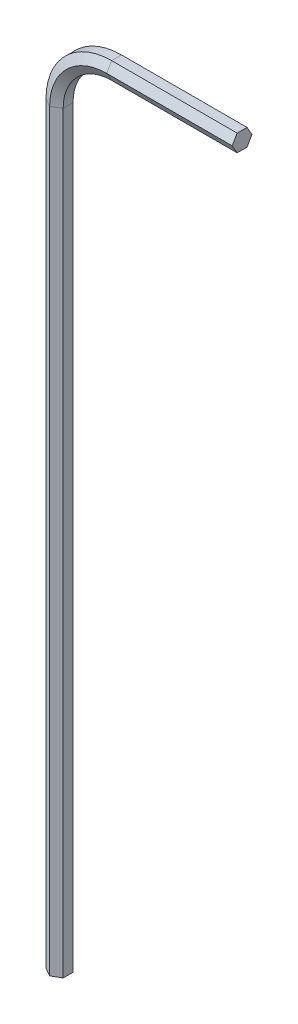
SolidWorks part; units mm, degrees
material "6061-T6 (SS)"
ref_plane "Front Plane" through (0, 0, 0) normal (0, 0, 1) x (1, 0, 0)
ref_plane "Top Plane" through (0, 0, 0) normal (0, 1, 0) x (1, 0, 0)
ref_plane "Right Plane" through (0, 0, 0) normal (1, 0, 0) x (0, 0, -1)
ref_axis "Axis1" through (0, 0, 55) along (0, 0, -1)
sketch "Sketch1" plane through (0, 0, 0) normal (0, 1, 0) x (1, 0, 0)
  line L1 (0.75, -0.433) -> (0.75, 0.433)
  line L2 (0.75, 0.433) -> (0, 0.866)
  line L3 (0, 0.866) -> (-0.75, 0.433)
  line L4 (-0.75, 0.433) -> (-0.75, -0.433)
  line L5 (-0.75, -0.433) -> (0, -0.866)
  line L6 (0, -0.866) -> (0.75, -0.433)
  circle A0 centre (0, 0) radius 0.75 construction
  dimension "D1" = 1.5
sketch "Sketch2" plane through (0, 0, 0) normal (0, 0, 1) x (1, 0, 0)
  line L0 (0, 0) -> (0, 66)
  line L1 (5, 71) -> (16, 71)
  arc A0 (0, 66) -> (5, 71) centre (5, 66) cw
  point P6 (0, 71)
  dimension "D3" = 5
  dimension "D1" = 71
  dimension "D2" = 16
sweep "Sweep1" add profiles "Sketch1" path "Sketch2"
